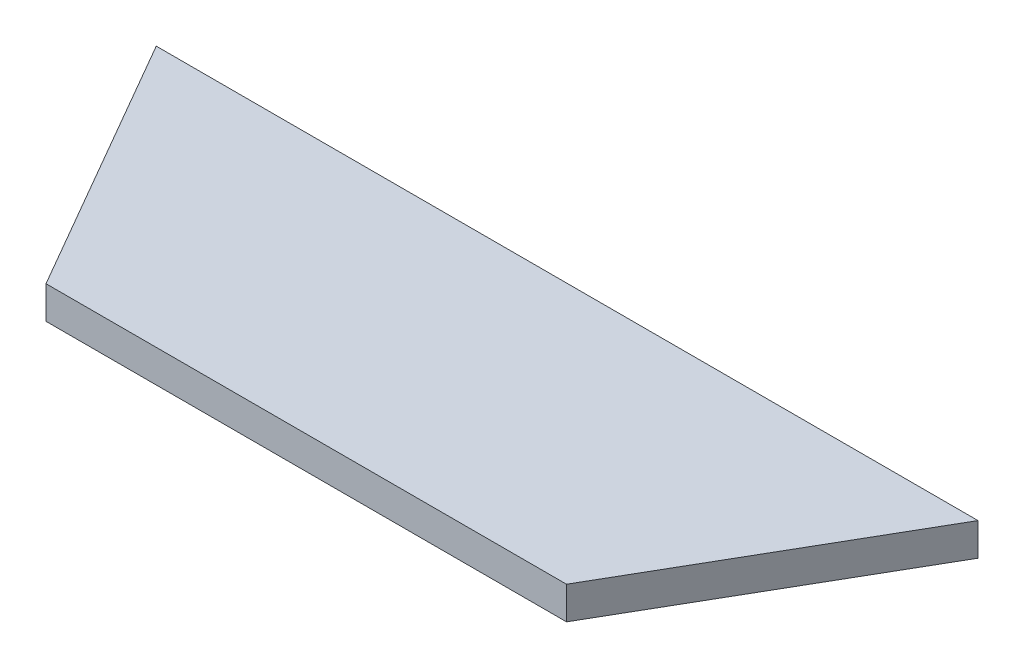
SolidWorks part; units mm, degrees
ref_plane "Спереди" through (0, 0, 0) normal (0, 0, 1) x (1, 0, 0)
ref_plane "Сверху" through (0, 0, 0) normal (0, 1, 0) x (1, 0, 0)
ref_plane "Справа" through (0, 0, 0) normal (1, 0, 0) x (0, 0, -1)
sketch "Эскиз1" plane through (0, 0, 0) normal (0, 1, 0) x (1, 0, 0)
  line L0 (0, 0) -> (79.812, 0)
  line L1 (79.812, 0) -> (102.906, 40)
  line L2 (102.906, 40) -> (-23.094, 40)
  line L3 (-23.094, 40) -> (0, 0)
  point P3 (0, 0)
  dimension "D1" = 40
extrude "Бобышка-Вытянуть1" add sketch "Эскиз1" along normal blind 5
